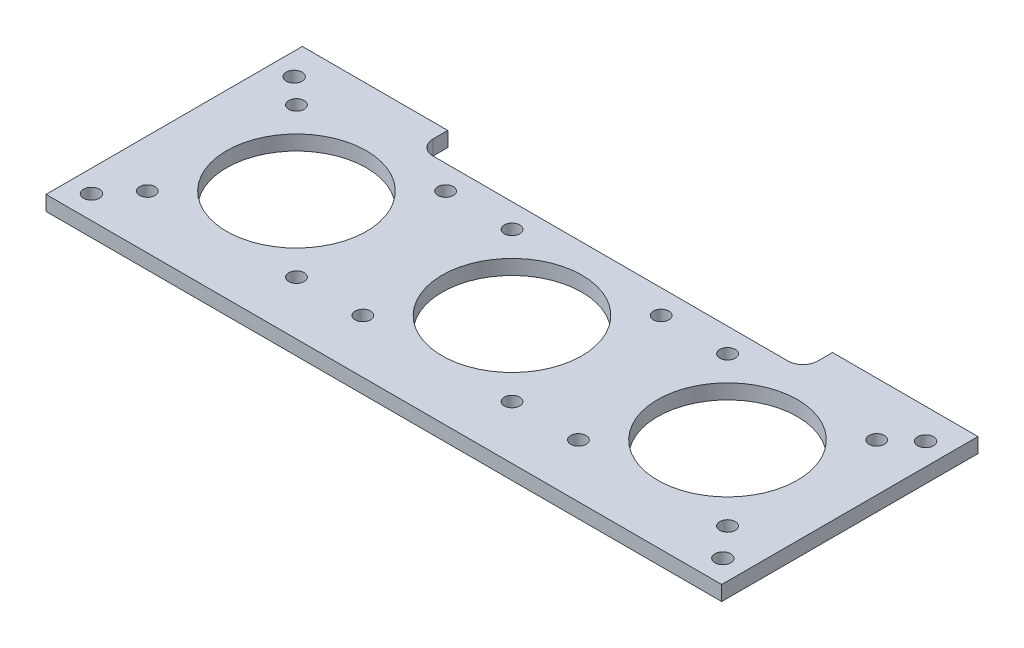
SolidWorks part; units mm, degrees
ref_plane "Front Plane" through (0, 0, 0) normal (0, 0, 1) x (1, 0, 0)
ref_plane "Top Plane" through (0, 0, 0) normal (0, 1, 0) x (1, 0, 0)
ref_plane "Right Plane" through (0, 0, 0) normal (1, 0, 0) x (0, 0, -1)
sketch "Sketch1" plane through (0, 0, 0) normal (0, 1, 0) x (1, 0, 0)
  line L0 (0, 0) -> (145, 55) construction
  line L1 (0, 0) -> (145, 0)
  line L2 (0, 0) -> (0, 55)
  line L3 (0, 55) -> (145, 55)
  line L4 (145, 0) -> (145, 55)
  point P5 (72.5, 27.5)
  dimension "D1" = 145
  dimension "D2" = 55
extrude "Boss-Extrude1" add sketch "Sketch1" along normal blind 3.175
ref_plane "Plane1" through (72.5, 0, 0) normal (1, 0, 0) x (0, 0, -1)
ref_plane "Plane2" through (0, 0, -27.5) normal (0, 0, -1) x (-1, 0, 0)
sketch "Sketch3" plane through (0, 3.175, 0) normal (0, 1, 0) x (1, 0, 0)
  line L0 (0, 0) -> (145, 55) construction
  point P4 (72.5, 27.5)
ref_axis "Axis1" through (72.5, 3.175, -27.5) along (0, 1, 0)
sketch "Sketch4" plane through (0, 0, 0) normal (0, -1, 0) x (1, 0, 0)
  line L0 (6.25, -7.5) -> (6.25, -47.5) construction
  line L1 (6.25, -47.5) -> (46.25, -47.5) construction
  line L2 (46.25, -47.5) -> (46.25, -7.5) construction
  line L3 (46.25, -7.5) -> (6.25, -7.5) construction
  line L4 (52.5, -7.5) -> (52.5, -47.5) construction
  line L5 (52.5, -47.5) -> (92.5, -47.5) construction
  line L6 (92.5, -47.5) -> (92.5, -7.5) construction
  line L7 (92.5, -7.5) -> (52.5, -7.5) construction
  line L8 (98.75, -7.5) -> (98.75, -47.5) construction
  line L9 (98.75, -47.5) -> (138.75, -47.5) construction
  line L10 (138.75, -47.5) -> (138.75, -7.5) construction
  line L11 (138.75, -7.5) -> (98.75, -7.5) construction
  line L12 (6.25, -7.5) -> (6.25, -47.5) construction
  line L13 (6.25, -47.5) -> (46.25, -47.5) construction
  line L14 (46.25, -47.5) -> (46.25, -7.5) construction
  line L15 (46.25, -7.5) -> (6.25, -7.5) construction
  line L16 (52.5, -7.5) -> (52.5, -47.5) construction
  line L17 (52.5, -47.5) -> (92.5, -47.5) construction
  line L18 (92.5, -47.5) -> (92.5, -7.5) construction
  line L19 (92.5, -7.5) -> (52.5, -7.5) construction
  line L20 (98.75, -7.5) -> (98.75, -47.5) construction
  line L21 (98.75, -47.5) -> (138.75, -47.5) construction
  line L22 (138.75, -47.5) -> (138.75, -7.5) construction
  line L23 (138.75, -7.5) -> (98.75, -7.5) construction
  line L24 (72.5, -55) -> (72.5, 0) construction
  line L25 (145, -55) -> (0, -55) construction
  line L26 (0, 0) -> (145, 0) construction
  line L27 (110.6, -3.175) -> (34.4, -3.175) construction
  line L28 (110.6, -6.35) -> (34.4, -6.35) construction
  line L29 (113.775, 0) -> (31.225, 0) construction
  line L30 (31.225, -3.175) -> (31.225, 0) construction
  line L31 (113.775, -3.175) -> (113.775, 0) construction
  line L32 (145, -27.5) -> (0, -27.5) construction
  line L33 (145, 0) -> (145, -55) construction
  line L34 (0, -55) -> (0, 0) construction
  line L35 (110.6, -51.825) -> (34.4, -51.825) construction
  line L36 (113.775, -51.825) -> (113.775, -55)
  line L37 (31.225, -51.825) -> (31.225, -55)
  line L38 (113.775, -55) -> (31.225, -55)
  line L39 (110.6, -48.65) -> (34.4, -48.65)
  circle A0 centre (10.25, -11.5) radius 1.651 construction
  circle A1 centre (10.25, -43.5) radius 1.651 construction
  circle A2 centre (42.25, -43.5) radius 1.651 construction
  circle A3 centre (26.25, -27.5) radius 15 construction
  circle A4 centre (42.25, -11.5) radius 1.651 construction
  circle A5 centre (56.5, -11.5) radius 1.651 construction
  circle A6 centre (56.5, -43.5) radius 1.651 construction
  circle A7 centre (88.5, -43.5) radius 1.651 construction
  circle A8 centre (88.5, -11.5) radius 1.651 construction
  circle A9 centre (72.5, -27.5) radius 15 construction
  circle A10 centre (102.75, -11.5) radius 1.651 construction
  circle A11 centre (102.75, -43.5) radius 1.651 construction
  circle A12 centre (134.75, -43.5) radius 1.651 construction
  circle A13 centre (134.75, -11.5) radius 1.651 construction
  circle A14 centre (118.75, -27.5) radius 15 construction
  circle A15 centre (10.25, -11.5) radius 1.651
  circle A16 centre (10.25, -43.5) radius 1.651
  circle A17 centre (42.25, -43.5) radius 1.651
  circle A18 centre (26.25, -27.5) radius 15
  circle A19 centre (42.25, -11.5) radius 1.651
  circle A20 centre (56.5, -11.5) radius 1.651
  circle A21 centre (56.5, -43.5) radius 1.651
  circle A22 centre (88.5, -43.5) radius 1.651
  circle A23 centre (88.5, -11.5) radius 1.651
  circle A24 centre (72.5, -27.5) radius 15
  circle A25 centre (102.75, -11.5) radius 1.651
  circle A26 centre (102.75, -43.5) radius 1.651
  circle A27 centre (134.75, -43.5) radius 1.651
  circle A28 centre (134.75, -11.5) radius 1.651
  circle A29 centre (118.75, -27.5) radius 15
  circle A30 centre (4.75, -5) radius 1.7 construction
  circle A31 centre (4.75, -48.5) radius 1.7 construction
  circle A32 centre (140.25, -5) radius 1.7 construction
  circle A33 centre (140.25, -48.5) radius 1.7 construction
  circle A34 centre (4.75, -5) radius 1.7
  circle A35 centre (4.75, -48.5) radius 1.7
  circle A36 centre (140.25, -5) radius 1.7
  circle A37 centre (140.25, -48.5) radius 1.7
  arc A38 (110.6, -6.35) -> (113.775, -3.175) centre (110.6, -3.175) ccw construction
  arc A39 (31.225, -3.175) -> (34.4, -6.35) centre (34.4, -3.175) ccw construction
  arc A40 (31.225, -51.825) -> (34.4, -48.65) centre (34.4, -51.825) cw
  arc A41 (110.6, -48.65) -> (113.775, -51.825) centre (110.6, -51.825) cw
  point P77 (72.5, -3.175)
  point P98 (72.5, -51.825)
  dimension "D1" = 3.175
  dimension "D2" = 76.2
  dimension "D3" = 3.175
extrude "Cut-Extrude1" cut sketch "Sketch4" against normal through all
